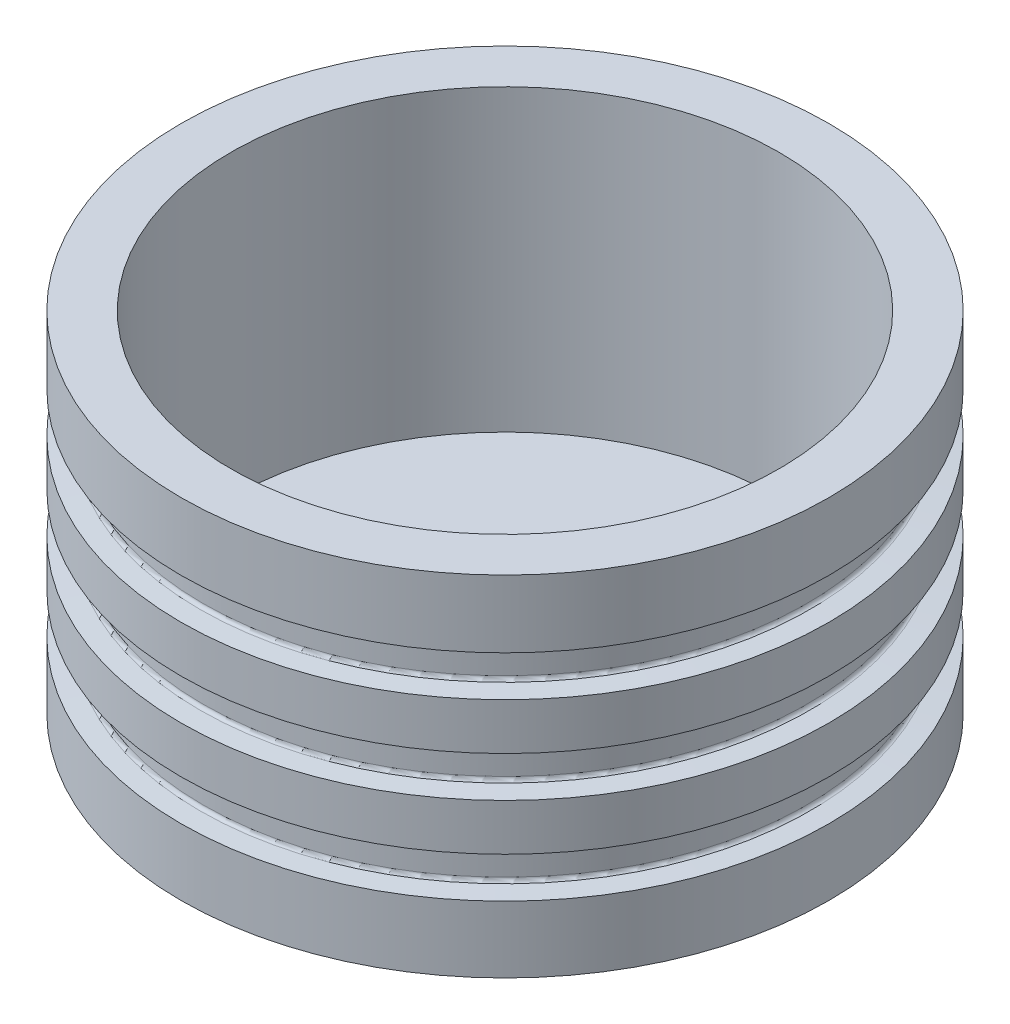
SolidWorks part; units mm, degrees
material "1060 Alloy"
ref_plane "Front Plane" through (0, 0, 0) normal (0, 0, 1) x (1, 0, 0)
ref_plane "Top Plane" through (0, 0, 0) normal (0, 1, 0) x (1, 0, 0)
ref_plane "Right Plane" through (0, 0, 0) normal (1, 0, 0) x (0, 0, -1)
sketch "Sketch1" plane through (0, 0, 0) normal (0, 0, 1) x (1, 0, 0)
  line L0 (0, 0) -> (0, 44.45) construction
  line L1 (-41.275, 0) -> (-41.275, 44.45)
  line L2 (-41.275, 0) -> (-6.35, 0)
  line L3 (-1.9133, 0) -> (-1.9133, 6.35)
  line L4 (-1.9133, 6.35) -> (-34.925, 6.35)
  line L5 (-34.925, 6.35) -> (-34.925, 44.45)
  line L6 (-34.925, 44.45) -> (-41.275, 44.45)
  line L7 (-1.9133, 0) -> (-1.9133, -12.7)
  line L8 (-1.9133, -12.7) -> (-6.35, -12.7)
  line L9 (-6.35, -12.7) -> (-6.35, 0)
  dimension "D1" = 44.45
  dimension "D2" = 1.9133
  dimension "D3" = 41.275
  dimension "D4" = 6.35
  dimension "D5" = 6.35
  dimension "D6" = 12.7
  dimension "D7" = 6.35
revolve "Revolve1" add sketch "Sketch1" angle 360 about L0
ref_plane "Plane1" through (0, 0, 0) normal (-1, 0, 0) x (0, 0, -1)
sketch "Sketch3" plane through (0, 0, 0) normal (-1, 0, 0) x (0, 0, -1)
  line L0 (38.8614, -27.1337) -> (41.3639, -26.9147)
  line L1 (41.3639, -26.9147) -> (41.3639, -32.1024)
  line L2 (41.3639, -32.1024) -> (38.8614, -31.8835)
  line L3 (38.4556, -31.4407) -> (38.4556, -27.5765)
  line L4 (0, 50) -> (0, -50) construction
  arc A0 (38.8614, -31.8835) -> (38.4556, -31.4407) centre (38.9001, -31.4407) cw
  arc A1 (38.4556, -27.5765) -> (38.8614, -27.1337) centre (38.9001, -27.5765) cw
ref_plane "Plane2" through (0, 0, 0) normal (-1, 0, 0) x (0, 0, -1)
sketch "Sketch5" plane through (0, 0, 0) normal (-1, 0, 0) x (0, 0, -1)
  line L0 (38.8614, -30.9088) -> (41.3639, -30.6898)
  line L1 (41.3639, -30.6898) -> (41.3639, -35.8775)
  line L2 (41.3639, -35.8775) -> (38.8614, -35.6586)
  line L3 (38.4556, -35.2157) -> (38.4556, -31.3516)
  line L4 (0, 50) -> (0, -50) construction
  line L5 (0, 50) -> (0, -50) construction
  line L6 (-41.275, -44.45) -> (41.275, -44.45) construction
  arc A0 (38.8614, -35.6586) -> (38.4556, -35.2157) centre (38.9001, -35.2157) cw
  arc A1 (38.4556, -31.3516) -> (38.8614, -30.9088) centre (38.9001, -31.3516) cw
  dimension "D1" = 8.5725
revolve "Groove for AS 568-234, O-Ring1" cut sketch "Sketch5"
ref_plane "Plane3" through (0, 0, 0) normal (-1, 0, 0) x (0, 0, -1)
sketch "Sketch7" plane through (0, 0, 0) normal (-1, 0, 0) x (0, 0, -1)
  line L0 (38.8614, -19.7963) -> (41.3639, -19.5773)
  line L1 (41.3639, -19.5773) -> (41.3639, -24.765)
  line L2 (41.3639, -24.765) -> (38.8614, -24.5461)
  line L3 (38.4556, -24.1032) -> (38.4556, -20.2391)
  line L4 (0, 50) -> (0, -50) construction
  line L5 (0, 50) -> (0, -50) construction
  line L6 (-41.275, -44.45) -> (41.275, -44.45) construction
  arc A0 (38.8614, -24.5461) -> (38.4556, -24.1032) centre (38.9001, -24.1032) cw
  arc A1 (38.4556, -20.2391) -> (38.8614, -19.7963) centre (38.9001, -20.2391) cw
  dimension "D1" = 19.685
revolve "Groove for AS 568-234, O-Ring2" cut sketch "Sketch7" angle 360 about L4 reverse direction yes
ref_plane "Plane4" through (0, 0, 0) normal (-1, 0, 0) x (0, 0, -1)
sketch "Sketch9" plane through (0, 0, 0) normal (-1, 0, 0) x (0, 0, -1)
  line L0 (38.8614, -8.6838) -> (41.3639, -8.4648)
  line L1 (41.3639, -8.4648) -> (41.3639, -13.6525)
  line L2 (41.3639, -13.6525) -> (38.8614, -13.4336)
  line L3 (38.4556, -12.9907) -> (38.4556, -9.1266)
  line L4 (0, 50) -> (0, -50) construction
  line L5 (0, 50) -> (0, -50) construction
  line L6 (-41.275, -44.45) -> (41.275, -44.45) construction
  arc A0 (38.8614, -13.4336) -> (38.4556, -12.9907) centre (38.9001, -12.9907) cw
  arc A1 (38.4556, -9.1266) -> (38.8614, -8.6838) centre (38.9001, -9.1266) cw
  dimension "D1" = 30.7975
revolve "Groove for AS 568-234, O-Ring3" cut sketch "Sketch9" angle 360 about L4 reverse direction yes
